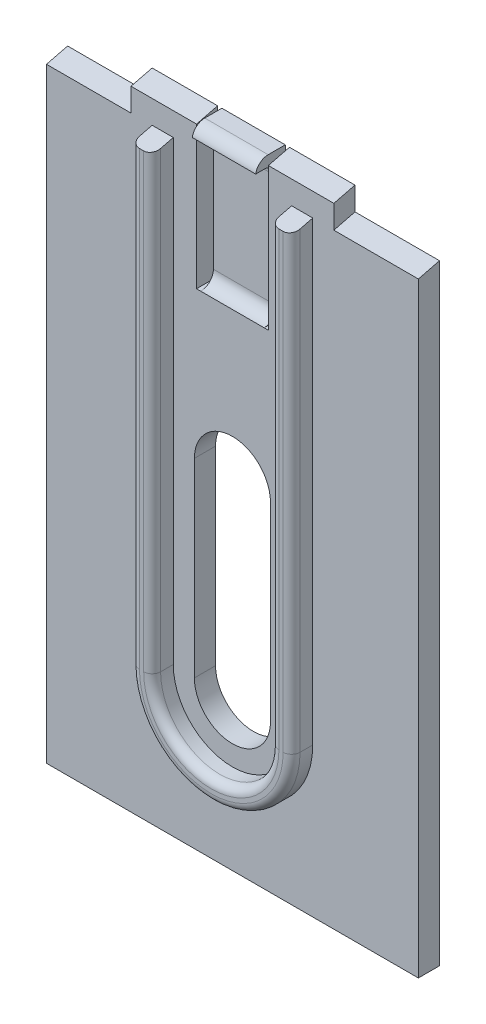
SolidWorks part; units mm, degrees
material "ABS"
ref_plane "Front Plane" through (0, 0, 0) normal (0, 0, 1) x (1, 0, 0)
ref_plane "Top Plane" through (0, 0, 0) normal (0, 1, 0) x (1, 0, 0)
ref_plane "Right Plane" through (0, 0, 0) normal (1, 0, 0) x (0, 0, -1)
sketch "Sketch1" plane through (0, 0, 0) normal (0, 0, 1) x (1, 0, 0)
  line L0 (0, 0) -> (0, 144.5)
  line L1 (0, 144.5) -> (20, 144.5)
  line L2 (20, 144.5) -> (20, 150)
  line L3 (20, 150) -> (35.5, 150)
  line L4 (35.5, 150) -> (35.5, 115)
  line L5 (35.5, 115) -> (36.5, 115)
  line L6 (36.5, 115) -> (36.5, 150)
  line L7 (36.5, 150) -> (51.5, 150)
  line L8 (51.5, 150) -> (51.5, 115)
  line L9 (51.5, 115) -> (52.5, 115)
  line L10 (52.5, 115) -> (52.5, 150)
  line L11 (52.5, 150) -> (68, 150)
  line L12 (68, 150) -> (68, 144.5)
  line L13 (68, 144.5) -> (88, 144.5)
  line L14 (88, 144.5) -> (88, 0)
  line L15 (88, 0) -> (0, 0)
  dimension "D1" = 144.5
  dimension "D2" = 20
  dimension "D3" = 15.5
  dimension "D4" = 1
  dimension "D5" = 35
  dimension "D6" = 15
  dimension "D7" = 1
  dimension "D8" = 15.5
  dimension "D9" = 5.5
  dimension "D11" = 20
extrude "Boss-Extrude1" add sketch "Sketch1" along normal blind 5
sketch "Sketch2" plane through (88, 0, 0) normal (1, 0, 0) x (0, 0, -1)
  line L4 (-5, 144.5) -> (0, 144.5)
  line L8 (0, 144.5) -> (-5, 143.2534)
  line L9 (-5, 0) -> (-5, 144.5) construction
  line L10 (-5, 143.2534) -> (-5, 144.5)
  dimension "D1" = 104
extrude "Cut-Extrude1" cut sketch "Sketch2" against normal blind 20
sketch "Sketch3" plane through (0, 0, 0) normal (-1, 0, 0) x (0, 0, 1)
  line L0 (5, 144.5) -> (0, 144.5)
  line L7 (5, 144.5) -> (5, 143.2534)
  line L8 (5, 144.5) -> (5, 0) construction
  line L9 (5, 143.2534) -> (0, 144.5)
  dimension "D1" = 104
extrude "Cut-Extrude2" cut sketch "Sketch3" against normal blind 20
sketch "Sketch4" plane through (68, 0, 0) normal (1, 0, 0) x (0, 0, -1)
  line L0 (0, 150) -> (-5, 148.7534)
  line L1 (-5, 143.2534) -> (-5, 150) construction
  line L2 (-5, 148.7534) -> (-5, 150)
  line L3 (-5, 150) -> (0, 150)
  dimension "D1" = 104
extrude "Cut-Extrude3" cut sketch "Sketch4" against normal blind 15.5
sketch "Sketch5" plane through (20, 0, 0) normal (-1, 0, 0) x (0, 0, 1)
  line L0 (0, 150) -> (5, 150)
  line L1 (5, 150) -> (0, 150) construction
  line L2 (5, 150) -> (5, 143.2534) construction
  line L3 (5, 150) -> (5, 148.7534)
  line L4 (5, 148.7534) -> (0, 150)
  dimension "D1" = 104
extrude "Cut-Extrude4" cut sketch "Sketch5" against normal blind 15.5
sketch "Sketch6" plane through (0, 0, 5) normal (0, 0, 1) x (1, 0, 0)
  line L0 (36.5, 147.5) -> (51.5, 147.5)
  line L1 (36.5, 150) -> (36.5, 115) construction
  line L2 (51.5, 115) -> (51.5, 150) construction
  line L3 (51.5, 147.5) -> (51.5, 115)
  line L4 (51.5, 115) -> (36.5, 115)
  line L5 (36.5, 115) -> (36.5, 147.5)
  line L6 (51.5, 150) -> (36.5, 150) construction
  dimension "D1" = 2.5
extrude "Cut-Extrude5" cut sketch "Sketch6" against normal blind 3
fillet "Fillet1" radius 3 1 edges at (44, 115, 2)
sketch "Sketch7" plane through (0, 0, 5) normal (0, 0, 1) x (1, 0, 0)
  line L0 (36.5, 147.5) -> (51.5, 147.5)
  line L1 (51.5, 147.5) -> (51.5, 150)
  line L2 (51.5, 150) -> (36.5, 150)
  line L3 (36.5, 150) -> (36.5, 147.5)
extrude "Boss-Extrude2" add sketch "Sketch7" along normal blind 2
fillet "Fillet2" radius 3 1 edges at (44, 147.5, 2)
fillet "Fillet3" radius 3 1 edges at (44, 150, 7)
sketch "Sketch8" plane through (0, 0, 5) normal (0, 0, 1) x (1, 0, 0)
  line L0 (35, 80) -> (35, 35)
  line L1 (53, 35) -> (53, 80)
  line L2 (0, 143.2534) -> (0, 0) construction
  line L3 (88, 0) -> (88, 143.2534) construction
  line L4 (51.5, 115) -> (36.5, 115) construction
  line L5 (0, 0) -> (88, 0) construction
  arc A0 (35, 80) -> (53, 80) centre (44, 80) cw
  arc A1 (35, 35) -> (53, 35) centre (44, 35) ccw
  dimension "D1" = 35
  dimension "D2" = 35
  dimension "D3" = 35
  dimension "D4" = 35
extrude "Cut-Extrude6" cut sketch "Sketch8" against normal blind 5
sketch "Sketch9" plane through (0, 0, 5) normal (0, 0, 1) x (1, 0, 0)
  line L0 (25, 143.2534) -> (25, 35.2534)
  line L1 (30, 143.2534) -> (30, 35.2534)
  line L2 (58, 143.2534) -> (58, 35.2534)
  line L3 (63, 143.2534) -> (63, 35.2534)
  line L4 (25, 143.2534) -> (30, 143.2534)
  line L5 (58, 143.2534) -> (63, 143.2534)
  line L6 (0, 143.2534) -> (0, 0) construction
  line L7 (88, 0) -> (88, 143.2534) construction
  line L8 (20, 143.2534) -> (0, 143.2534) construction
  line L9 (68, 143.2534) -> (88, 143.2534) construction
  arc A2 (30, 35.2534) -> (58, 35.2534) centre (44, 35.2534) ccw
  arc A3 (25, 35.2534) -> (63, 35.2534) centre (44, 35.2534) ccw
  point P16 (27.5, 143.2534)
  dimension "D1" = 25
  dimension "D2" = 25
  dimension "D3" = 5
  dimension "D4" = 5
  dimension "D5" = 108
  dimension "D6" = 0
  dimension "D7" = 0
extrude "Boss-Extrude3" add sketch "Sketch9" along normal blind 5
sketch "Sketch10" plane through (25, 0, 0) normal (-1, 0, 0) x (0, 0, 1)
  line L0 (5, 143.2534) -> (10, 142.0067)
  line L1 (10, 143.2534) -> (10, 35.2534) construction
  line L2 (10, 142.0067) -> (10, 143.2534)
  line L3 (10, 143.2534) -> (5, 143.2534)
  line L4 (5, 143.2534) -> (5, 35.2534) construction
  dimension "D1" = 76
extrude "Cut-Extrude7" cut sketch "Sketch10" against normal blind 5
sketch "Sketch11" plane through (63, 0, 0) normal (1, 0, 0) x (0, 0, -1)
  line L0 (-5, 143.2534) -> (-10, 142.0067)
  line L1 (-10, 142.0067) -> (-10, 143.2534)
  line L2 (-10, 143.2534) -> (-5, 143.2534)
  line L3 (-5, 35.2534) -> (-5, 143.2534) construction
  dimension "D1" = 76
extrude "Cut-Extrude8" cut sketch "Sketch11" against normal blind 5
fillet "Fillet4" radius 2 3 edges at (25, 88.63, 10) (44, 16.2534, 10) (63, 88.63, 10)
fillet "Fillet5" radius 2 3 edges at (58, 88.63, 10) (44, 21.2534, 10) (30, 88.63, 10)
